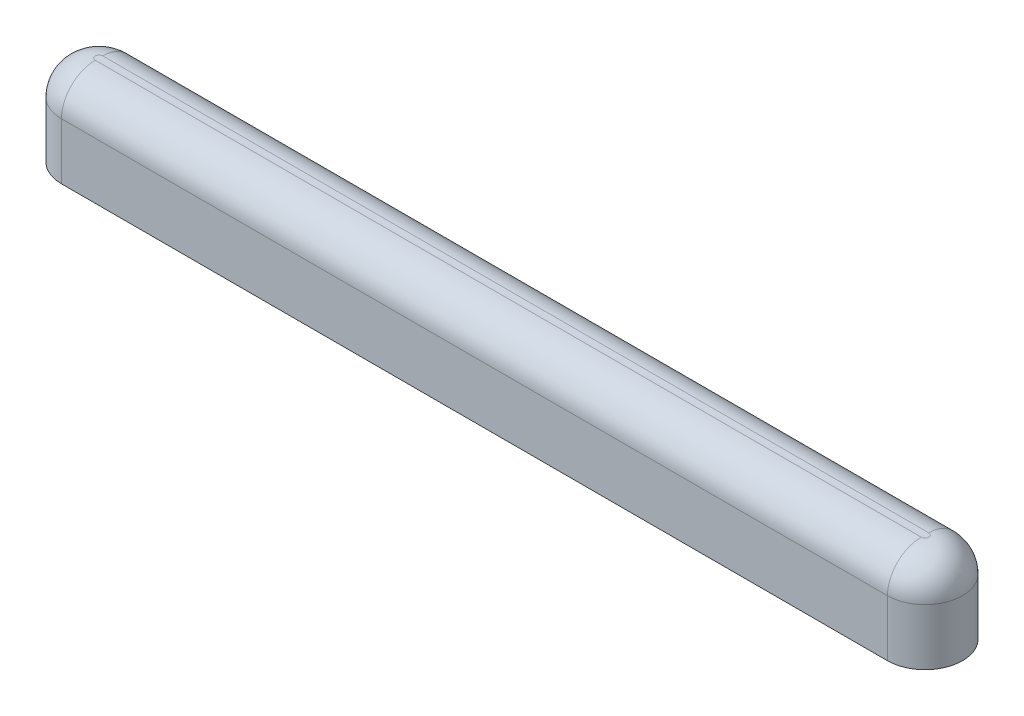
SolidWorks part; units mm, degrees
material "ABS"
ref_plane "Front Plane" through (0, 0, 0) normal (0, 0, 1) x (1, 0, 0)
ref_plane "Top Plane" through (0, 0, 0) normal (0, 1, 0) x (1, 0, 0)
ref_plane "Right Plane" through (0, 0, 0) normal (1, 0, 0) x (0, 0, -1)
sketch "Sketch1" plane through (0, 0, 0) normal (0, 1, 0) x (1, 0, 0)
  line L0 (-55, 0) -> (55, 0) construction
  line L1 (-55, 5) -> (55, 5)
  line L2 (-55, -5) -> (55, -5)
  arc A0 (-55, 5) -> (-55, -5) centre (-55, 0) ccw
  arc A1 (55, -5) -> (55, 5) centre (55, 0) ccw
  point P2 (0, 0)
  dimension "D1" = 10
  dimension "D2" = 110
extrude "Boss-Extrude1" add sketch "Sketch1" along normal blind 12
fillet "Fillet1" radius 4.5 4 edges at (0, 12, -5) (60, 12, 0) (0, 12, 5) (-60, 12, 0)
